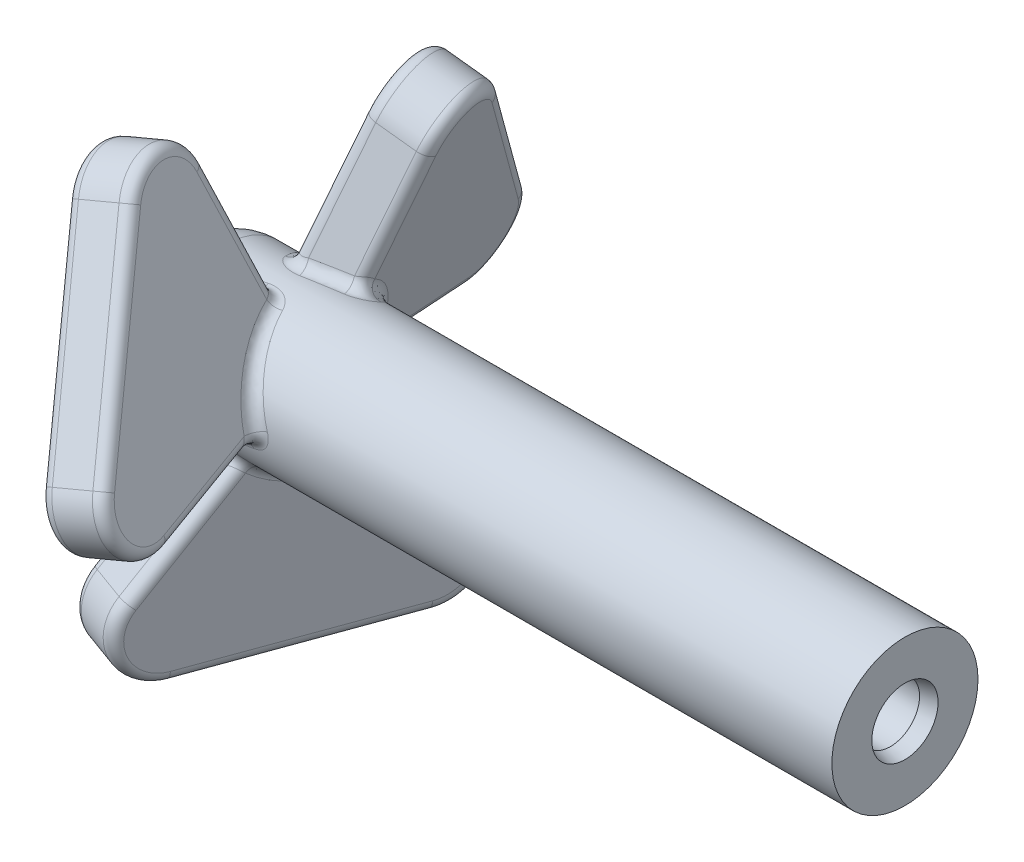
SolidWorks part; units mm, degrees
ref_plane "Front Plane" through (0, 0, 0) normal (0, 0, 1) x (1, 0, 0)
ref_plane "Top Plane" through (0, 0, 0) normal (0, 1, 0) x (1, 0, 0)
ref_plane "Right Plane" through (0, 0, 0) normal (1, 0, 0) x (0, 0, -1)
sketch "Sketch1" plane through (0, 0, 0) normal (0, 0, 1) x (1, 0, 0)
  line L0 (0, 0) -> (-12.7, 0)
  line L1 (-12.7, 0) -> (-12.7, 1.27)
  line L2 (-12.7, 1.27) -> (0, 1.27)
  line L3 (0, 0) -> (0, 21.9283) construction
  line L4 (20.7794, 0) -> (0, 0) construction
  line L7 (0, 0) -> (0, 1.27)
  dimension "D2" = 1.27
  dimension "D4" = 12.7
revolve "Revolve1" add sketch "Sketch1" angle 360 about L4
ref_axis "rotation_axis" through (0.635, 0, 0) along (-1, 0, 0)
ref_plane "Plane1" through (-10.795, 0, 0) normal (-1, 0, 0) x (0, 0, 1)
ref_axis "blade_axis" through (-10.795, 55.0126, 0) along (0, -1, 0)
ref_plane "blade_plane" through (-9.5322, 0, -3.4694) normal (-0.9397, 0, -0.342) x (-0.342, 0, 0.9397)
sketch "Sketch2" plane through (-9.5322, 0, -3.4694) normal (-0.9397, 0, -0.342) x (-0.342, 0, 0.9397)
  line L0 (7.3386, -3.9795) -> (3.6921, -1.9897) construction
  line L1 (0.0456, -3.9795) -> (7.3386, -3.9795) construction
  line L2 (7.3386, -3.9795) -> (3.6921, 0) construction
  line L3 (3.6921, -3.9795) -> (3.6921, 0) construction
  line L4 (3.6921, 55.0126) -> (3.6921, -54.9874) construction
  line L5 (-0.2172, 0) -> (4.5608, 0) construction
  line L6 (3.6921, 0) -> (6.0763, -2.6019)
  line L7 (3.6921, 0) -> (1.3079, -2.6019)
  line L8 (1.9141, -3.9795) -> (5.4701, -3.9795)
  line L9 (0.0456, -3.9795) -> (3.6921, -1.9897) construction
  line L10 (0.0456, -3.9795) -> (3.6921, 0) construction
  circle A0 centre (3.6921, 0) radius 5.3975 construction
  arc A1 (5.4701, -3.9795) -> (6.0763, -2.6019) centre (5.4701, -3.1573) ccw
  arc A2 (1.9141, -3.9795) -> (1.3079, -2.6019) centre (1.9141, -3.1573) cw
  dimension "D2" = 10.795
  dimension "D1" = 42.5
  dimension "D4" = 1.778
extrude "Boss-Extrude1" add sketch "Sketch2" along normal mid plane 1.016
pattern_circular "CirPattern1" count 3 over 360 about axis through (0.635, 0, 0) along (-1, 0, 0) of "Boss-Extrude1"
fillet "Fillet1" radius 0.889 1 edges at (-12.7, 0, -1.27)
fillet "Fillet3" radius 0.1905 42 edges at (-11.0966, -0.9624, 0.8287) (-10.4934, -0.9624, -0.8287) (-11.8435, -1.8225, 1.3955) (-11.2724, -3.9795, -0.1737) (-10.7281, -1.7366, -1.6691) (-11.2877, -1.2632, -0.1317) (-11.0966, -0.2365, -1.2478) (-10.4934, 1.1989, -0.4191) (-11.0966, 1.1989, 0.4191) (-10.4934, -0.2365, 1.2478) (-11.8435, 2.1198, 0.8805) (-11.2724, 1.8393, 3.5332) (-10.7281, -0.5772, 2.3384) (-11.2877, 0.5176, 1.1598) (-11.8435, -0.2973, -2.2761) (-11.2724, 2.1402, -3.3594) (-10.7281, 2.3137, -0.6694) (-11.2877, 0.7456, -1.0281) (-10.3176, 1.8393, -3.5332) (-10.8619, -0.5772, -2.3384) (-10.3023, 0.5176, -1.1598) (-9.7465, 2.1198, -0.8805) (-10.3176, 2.1402, 3.3594) (-10.8619, 2.3137, 0.6694) (-10.3023, 0.7456, 1.0281) (-9.7465, -0.2973, 2.2761) (-10.3176, -3.9795, 0.1737) (-10.8619, -1.7366, 1.6691) (-10.3023, -1.2632, 0.1317) (-9.7465, -1.8225, -1.3955) (-12.1379, 3.6531, 1.919) (-10.4069, -0.4656, 4.2969) (-12.1379, -0.1647, -4.1231) (-10.4069, 3.954, -1.7452) (-9.4521, 3.6531, -1.919) (-11.1831, -0.4656, -4.2969) (-9.4521, -0.1647, 4.1231) (-11.1831, 3.954, 1.7452) (-9.4521, -3.4884, -2.2042) (-11.1831, -3.4884, 2.5517) (-12.1379, -3.4884, 2.2042) (-10.4069, -3.4884, -2.5517)
sketch "Sketch5" plane through (0, 0, 0) normal (1, 0, 0) x (0, 0, -1)
  line L0 (-0.336, 0.381) -> (0.336, 0.381)
  line L1 (-0.7367, -0.508) -> (1.5604, -0.508) construction
  arc A0 (-0.336, 0.381) -> (0.336, 0.381) centre (0, 0) ccw
  dimension "D1" = 1.016
  dimension "D2" = 0.889
extrude "Cut-Extrude1" [suppressed] cut sketch "Sketch5" against normal blind 3.81
sketch "Sketch6" [suppressed] plane through (0, 0, 0) normal (1, 0, 0) x (0, 0, -1)
  circle A0 centre (0, 0) radius 0.508
  arc A1 (-0.336, 0.381) -> (0.336, 0.381) centre (0, 0) ccw construction
extrude "Cut-Extrude2" [suppressed] cut sketch "Sketch6" against normal blind 0.889
chamfer "Chamfer4" [suppressed] distance 0.254 angle 15
sketch "Sketch7" plane through (0, 0, 0) normal (1, 0, 0) x (0, 0, -1)
  line L1 (0.127, 1.016) -> (-0.127, 1.016)
  line L2 (0.127, 1.016) -> (0.127, 1.86)
  line L3 (0.127, 1.86) -> (-0.127, 1.86)
  line L4 (-0.127, 1.016) -> (-0.127, 1.86)
  line L5 (0.127, 1.016) -> (-0.127, 1.86) construction
  line L6 (0.127, 1.86) -> (-0.127, 1.016) construction
  point P0 (0, 1.438)
  dimension "D1" = 1.016
  dimension "D2" = 0.254
extrude "Cut-Extrude3" [suppressed] cut sketch "Sketch7" against normal blind 0.127
sketch "Sketch8" plane through (0, 0, 0) normal (1, 0, 0) x (0, 0, -1)
  circle A0 centre (0, 0) radius 0.508
  dimension "D1" = 1.016
extrude "Cut-Extrude4" cut sketch "Sketch8" against normal blind 3.81
chamfer "Chamfer5" distance 0.254 angle 15 1 edges at (0, 0, -0.508) first distance on face at (-3.81, 0, -0.508)
